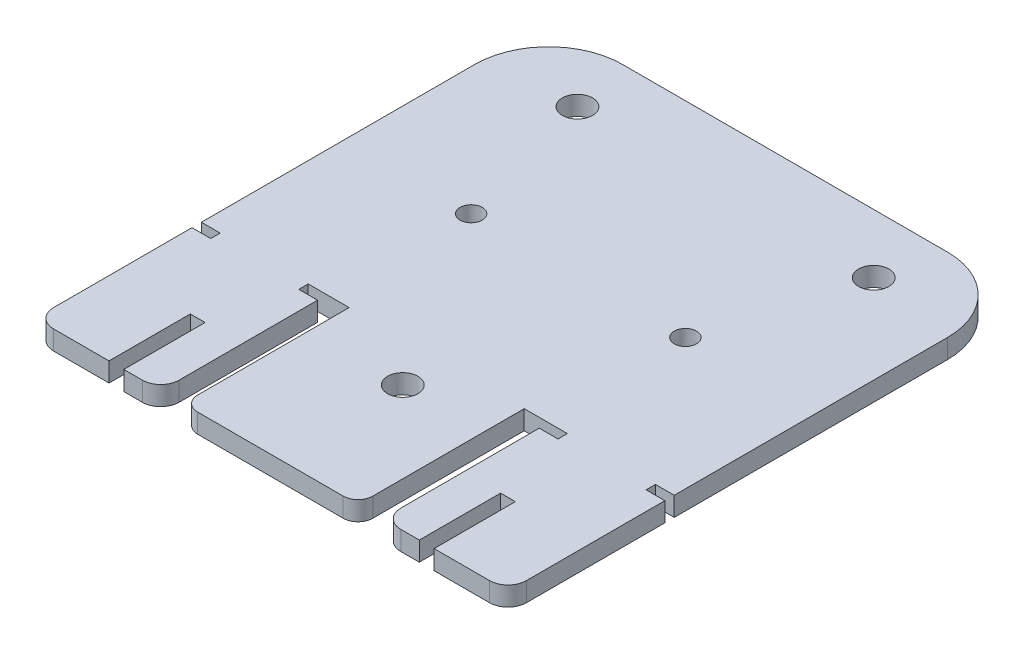
SolidWorks part; units mm, degrees
ref_plane "Front Plane" through (0, 0, 0) normal (0, 0, 1) x (1, 0, 0)
ref_plane "Top Plane" through (0, 0, 0) normal (0, 1, 0) x (1, 0, 0)
ref_plane "Right Plane" through (0, 0, 0) normal (1, 0, 0) x (0, 0, -1)
sketch "Sketch1" plane through (0, 0, 0) normal (0, 1, 0) x (1, 0, 0)
  line L0 (11.7, -23.5) -> (32, -23.5)
  line L1 (-32, -23.5) -> (-12, -23.5)
  line L2 (-32, -23.5) -> (-32, 13.5)
  line L3 (-22, 23.5) -> (22, 23.5)
  line L4 (32, -23.5) -> (32, 13.5)
  line L5 (-32, -23.5) -> (32, 23.5) construction
  line L6 (-32, 23.5) -> (32, -23.5) construction
  line L8 (-12, -23.5) -> (-12, -46)
  line L9 (-12, -46) -> (11.7, -46)
  line L10 (11.7, -23.5) -> (11.7, -46)
  arc A0 (-32, 13.5) -> (-22, 23.5) centre (-22, 13.5) cw
  arc A1 (32, 13.5) -> (22, 23.5) centre (22, 13.5) ccw
  point P0 (0, 0)
  dimension "D6" = 10
  dimension "D7" = 10
  dimension "D1" = 64
  dimension "D2" = 47
  dimension "D3" = 20
  dimension "D4" = 23.7
  dimension "D5" = 22.5
extrude "Main Body" add sketch "Sketch1" along normal blind 2.6
sketch "Sketch2" plane through (0, 2.6, 0) normal (0, 1, 0) x (1, 0, 0)
  line L0 (22, 23.5) -> (-22, 23.5) construction
  line L1 (-32, 13.5) -> (-32, -23.5) construction
  line L2 (0, 0) -> (0, 23.5) construction
  line L3 (32, -23.5) -> (32, 13.5) construction
  line L4 (0.7, -31) -> (0.7, -32.3) construction
  line L5 (0.7, -32.3) -> (14.26, -32.3) construction
  line L6 (-12, -23.5) -> (-12, -46) construction
  line L7 (14.26, -32.3) -> (14.26, -4.25) construction
  line L8 (-14.74, -4.25) -> (-16.24, -4.25) construction
  line L9 (14.26, -4.25) -> (15.76, -4.25) construction
  circle A0 centre (-20.1, 15.5) radius 2.05
  circle A1 centre (20, 15.5) radius 2.05
  circle A3 centre (-14.74, -4.25) radius 1.5
  circle A4 centre (14.26, -4.25) radius 1.5
  circle A6 centre (0.7, -28.95) radius 2.05
  dimension "D1" = 4.1
  dimension "D4" = 4.1
  dimension "D7" = 29
  dimension "D8" = 3
  dimension "D9" = 3
  dimension "D10" = 13.56
  dimension "D11" = 4.1
  dimension "D2" = 8
  dimension "D3" = 11.9
  dimension "D5" = 8
  dimension "D6" = 12
  dimension "D12" = 28.05
  dimension "D13" = 1.3
  dimension "D20" = 12.7
  dimension "D21" = 44.45
extrude "Screw holes" cut sketch "Sketch2" against normal through all both and the other way through all
fillet "Main lower body Fillet" radius 2 2 edges at (11.7, 1.3, 46) (-12, 1.3, 46)
sketch "Sketch4" plane through (0, 2.6, 0) normal (0, 1, 0) x (1, 0, 0)
  line L1 (-32, -23.5) -> (-15, -23.5)
  line L2 (-32, -23.5) -> (-32, -21)
  line L3 (-32, -21) -> (-15, -21)
  line L4 (-15, -23.5) -> (-15, -21)
  line L5 (32, -23.5) -> (15, -23.5)
  line L6 (32, -23.5) -> (32, -21)
  line L7 (32, -21) -> (15, -21)
  line L8 (15, -23.5) -> (15, -21)
  dimension "D1" = 2.5
  dimension "D2" = 2.5
  dimension "D3" = 17
  dimension "D4" = 17
sketch "Sketch5" plane through (0, 0, 23.5) normal (0, 0, 1) x (1, 0, 0)
  line L0 (-32, 0) -> (-12, 0) construction
  line L1 (-32, 2.6) -> (-15, 2.6)
  line L2 (-32, 2.6) -> (-32, 0)
  line L3 (-32, 0) -> (-15, 0)
  line L4 (-15, 2.6) -> (-15, 0)
  line L5 (11.7, 0) -> (32, 0) construction
  line L6 (32, 2.6) -> (15, 2.6)
  line L7 (32, 2.6) -> (32, 0)
  line L8 (32, 0) -> (15, 0)
  line L9 (15, 2.6) -> (15, 0)
  dimension "D1" = 17
  dimension "D2" = 17
extrude "Boss-Extrude1" add sketch "Sketch5" along normal blind 22.5
sketch "Sketch6" plane through (0, 2.6, 0) normal (0, 1, 0) x (1, 0, 0)
  line L0 (-15, -46) -> (-32, -46) construction
  line L1 (-20, -46) -> (-22, -46)
  line L2 (-20, -46) -> (-20, -35)
  line L3 (-20, -35) -> (-22, -35)
  line L4 (-22, -46) -> (-22, -35)
  line L5 (32, -46) -> (15, -46) construction
  line L6 (22, -46) -> (20, -46)
  line L7 (22, -46) -> (22, -35)
  line L8 (22, -35) -> (20, -35)
  line L9 (20, -46) -> (20, -35)
  line L10 (-32, 13.5) -> (-32, -46) construction
  line L11 (32, -46) -> (32, 13.5) construction
  point P16 (21, -35)
  dimension "D1" = 12
  dimension "D2" = 12
  dimension "D3" = 10
  dimension "D4" = 10
  dimension "D5" = 11
  dimension "D6" = 11
extrude "Cut-Extrude1" cut sketch "Sketch6" against normal blind 22.5
fillet "Fillet2" radius 2.5 4 edges at (-32, 1.3, 46) (-15, 1.3, 46) (15, 1.3, 46) (32, 1.3, 46)
sketch "Sketch7" plane through (0, 2.6, 0) normal (0, 1, 0) x (1, 0, 0)
  line L0 (32, -23.5) -> (15, -23.5) construction
  line L1 (-32, -23.5) -> (-29.46, -23.5)
  line L2 (-32, -23.5) -> (-32, -24.77)
  line L3 (-32, -24.77) -> (-29.46, -24.77)
  line L4 (-29.46, -23.5) -> (-29.46, -24.77)
  line L5 (32, -23.5) -> (29.46, -23.5)
  line L6 (32, -23.5) -> (32, -24.77)
  line L7 (32, -24.77) -> (29.46, -24.77)
  line L8 (29.46, -23.5) -> (29.46, -24.77)
  line L10 (-15, -23.5) -> (-17.54, -23.5)
  line L11 (-15, -23.5) -> (-15, -24.77)
  line L12 (-15, -24.77) -> (-17.54, -24.77)
  line L13 (-17.54, -23.5) -> (-17.54, -24.77)
  line L14 (15, -23.5) -> (17.54, -23.5)
  line L15 (15, -23.5) -> (15, -24.77)
  line L16 (15, -24.77) -> (17.54, -24.77)
  line L17 (17.54, -23.5) -> (17.54, -24.77)
  dimension "D1" = 2.54
  dimension "D2" = 2.54
  dimension "D3" = 1.27
  dimension "D4" = 1.27
  dimension "D5" = 2.54
  dimension "D6" = 2.54
  dimension "D7" = 1.27
  dimension "D8" = 1.27
extrude "Cut-Extrude2" cut sketch "Sketch7" against normal through all
